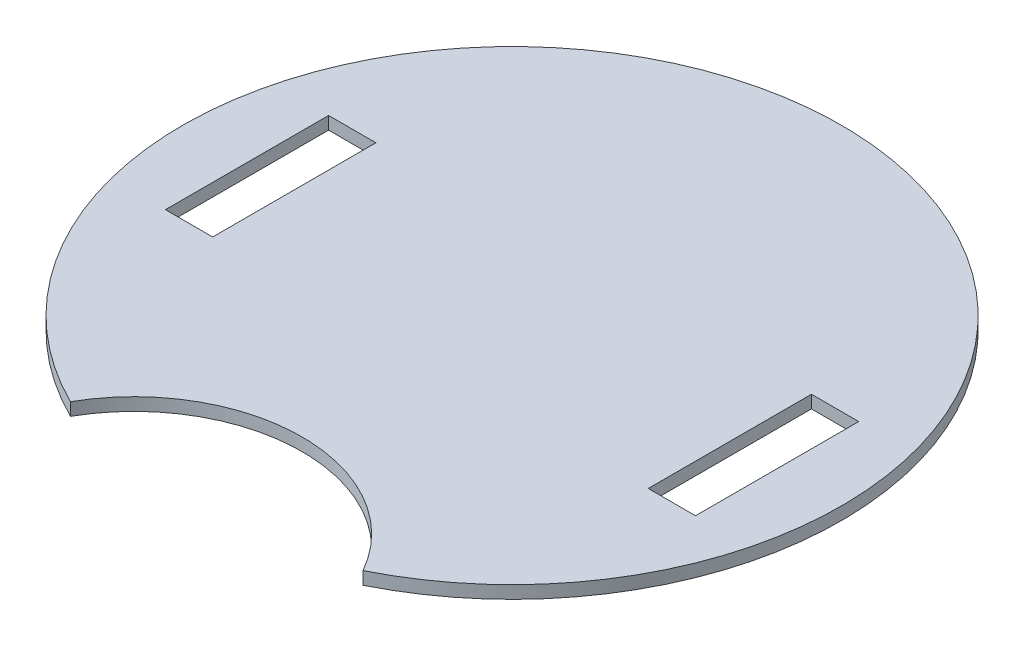
SolidWorks part; units mm, degrees
ref_plane "Front Plane" through (0, 0, 0) normal (0, 0, 1) x (1, 0, 0)
ref_plane "Top Plane" through (0, 0, 0) normal (0, 1, 0) x (1, 0, 0)
ref_plane "Right Plane" through (0, 0, 0) normal (1, 0, 0) x (0, 0, -1)
sketch "Sketch1" plane through (0, 0, 0) normal (0, 1, 0) x (1, 0, 0)
  line L0 (0, -86.0416) -> (-33.2911, -67.2064) construction
  line L1 (0, -86.0416) -> (0, 0) construction
  arc A0 (33.2911, -67.2064) -> (-33.2911, -67.2064) centre (0, 0) ccw
  arc A1 (33.2911, -67.2064) -> (-33.2911, -67.2064) centre (0, -86.0416) ccw
  dimension "D1" = 150
  dimension "D2" = 76.5
  dimension "D3" = 60.5
extrude "Boss-Extrude1" add sketch "Sketch1" along normal blind 2.9
sketch "solenoid placement" plane through (0, 2.9, 0) normal (0, 1, 0) x (1, 0, 0)
  line L0 (0, 0) -> (0, -36) construction
  line L1 (0, -36) -> (0, -47.7916) construction
  line L2 (-19, -36) -> (19, -36)
  line L3 (-19, -36) -> (-19, 28.4)
  line L4 (-19, 28.4) -> (19, 28.4)
  line L5 (19, -36) -> (19, 28.4)
  circle A1 centre (0, 0) radius 75 construction
  arc A2 (33.2911, -67.2064) -> (-33.2911, -67.2064) centre (0, 0) ccw construction
  arc A3 (33.2911, -67.2064) -> (-33.2911, -67.2064) centre (0, -86.0416) ccw construction
  dimension "D1" = 64.4
  dimension "D2" = 36
  dimension "D4" = 38
sketch "Sketch2" plane through (0, 2.9, 0) normal (0, 1, 0) x (1, 0, 0)
  line L1 (-60.0227, 18.2695) -> (-49.8627, 18.2695) construction
  line L2 (-60.0227, 18.2695) -> (-60.0227, -18.2695) construction
  line L3 (-60.0227, -18.2695) -> (-49.8627, -18.2695) construction
  line L4 (-49.8627, 18.2695) -> (-49.8627, -18.2695) construction
  line L8 (-60.3227, -18.5695) -> (-49.5627, -18.5695)
  line L9 (-49.5627, 18.5695) -> (-49.5627, -18.5695)
  line L10 (-60.3227, 18.5695) -> (-49.5627, 18.5695)
  line L11 (-60.3227, 18.5695) -> (-60.3227, -18.5695)
  line L12 (0, 0) -> (0, 75) construction
  line L13 (49.8627, 18.2695) -> (49.8627, -18.2695) construction
  line L14 (60.0227, -18.2695) -> (49.8627, -18.2695) construction
  line L15 (60.0227, 18.2695) -> (60.0227, -18.2695) construction
  line L16 (60.0227, 18.2695) -> (49.8627, 18.2695) construction
  line L17 (60.3227, 18.5695) -> (60.3227, -18.5695)
  line L18 (60.3227, 18.5695) -> (49.5627, 18.5695)
  line L19 (49.5627, 18.5695) -> (49.5627, -18.5695)
  line L20 (60.3227, -18.5695) -> (49.5627, -18.5695)
  arc A0 (33.2911, -67.2064) -> (-33.2911, -67.2064) centre (0, 0) ccw construction
extrude "Cut-Extrude1" cut sketch "Sketch2" against normal through all
equation "\"smallPulleyTeeth\"= 15"
equation "\"largePulleyTeeth\"= 30"
equation "\"eighthThick\"= 2.9mm"
equation "\"sixteenthThick\" = 1.7mm"
equation "\"wheelEighthThick\"=3.0mm"
equation "\"quarterThick\"=5.6mm"
equation "\"OD\" = 150mm"
equation "\"puckAngle\" = 60.5deg"
equation "\"D1@Sketch1\"=\"OD\""
equation "\"puckDiam\" = 76.5mm"
equation "\"D2@Sketch1\"=\"puckDiam\""
equation "\"D3@Sketch1\"=\"puckAngle\""
equation "\"D1@Boss-Extrude1\"=\"eighthThick\""
equation "\"axlePress\" = 5.8mm"
equation "\"press\" = 0.2mm"
equation "\"wheelClear\" = 0.3mm"
equation "\"D1@Sketch2\"=\"wheelClear\""
